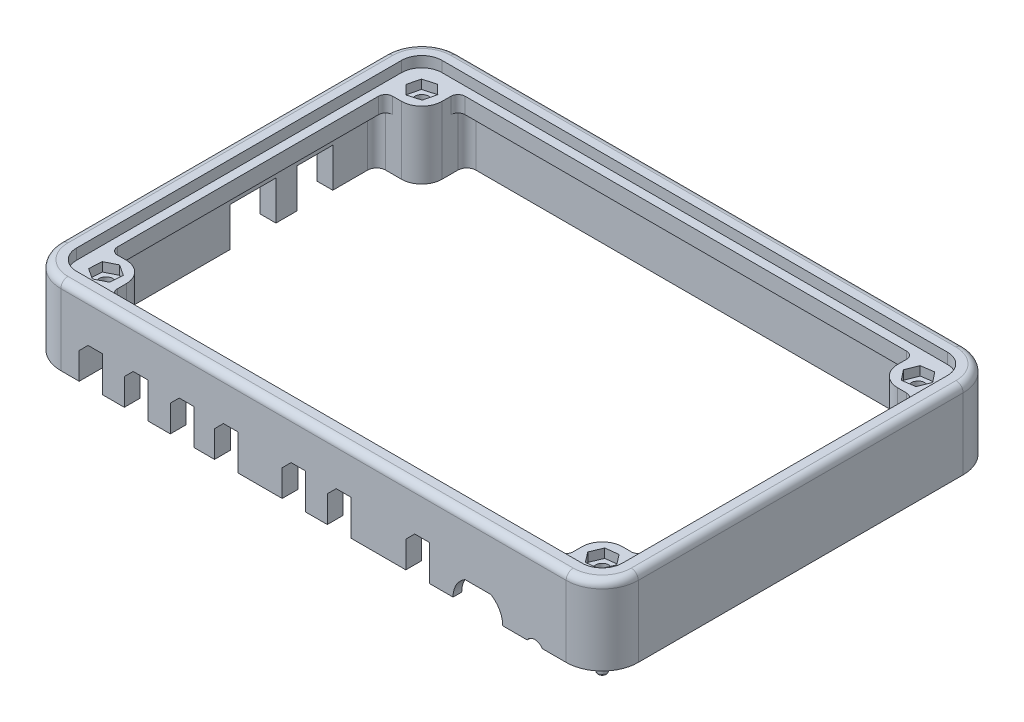
SolidWorks part; units mm, degrees
ref_plane "Front Plane" through (0, 0, 0) normal (0, 0, 1) x (1, 0, 0)
ref_plane "Top Plane" through (0, 0, 0) normal (0, 1, 0) x (1, 0, 0)
ref_plane "Right Plane" through (0, 0, 0) normal (1, 0, 0) x (0, 0, -1)
sketch "Sketch1" plane through (0, 0, 0) normal (0, 1, 0) x (1, 0, 0)
  line L1 (-71.12, 55.88) -> (71.12, 55.88)
  line L2 (-81.28, 45.72) -> (-81.28, -45.72)
  line L3 (-71.12, -55.88) -> (71.12, -55.88)
  line L4 (81.28, 45.72) -> (81.28, -45.72)
  line L5 (-81.28, 55.88) -> (81.28, -55.88) construction
  line L6 (-81.28, -55.88) -> (81.28, 55.88) construction
  arc A0 (-81.28, -45.72) -> (-71.12, -55.88) centre (-71.12, -45.72) ccw
  arc A1 (71.12, -55.88) -> (81.28, -45.72) centre (71.12, -45.72) ccw
  arc A2 (71.12, 55.88) -> (81.28, 45.72) centre (71.12, 45.72) cw
  arc A3 (-71.12, 55.88) -> (-81.28, 45.72) centre (-71.12, 45.72) ccw
  point P0 (0, 0)
  dimension "D3" = 10.16
  dimension "D1" = 162.56
  dimension "D2" = 111.76
extrude "Boss-Extrude1" add sketch "Sketch1" along normal blind 40
sketch "Sketch2" plane through (0, 0, 55.88) normal (0, 0, 1) x (1, 0, 0)
  line L0 (-71.12, 12) -> (71.12, 12) construction
  line L1 (-71.12, 40) -> (-71.12, 0) construction
  line L2 (71.12, 40) -> (71.12, 0) construction
  line L3 (71.12, 18) -> (27.6283, 18) construction
  line L4 (71.12, 28) -> (-71.12, 28) construction
  line L5 (-71.12, 40) -> (71.12, 40) construction
  line L6 (-71.12, 0) -> (71.12, 0) construction
  line L7 (-71.12, 11) -> (71.12, 11) construction
  line L8 (50.798, 16.68) -> (71.12, 16.68) construction
  line L9 (71.12, 9.42) -> (-71.12, 9.42) construction
  line L10 (76.28, 40) -> (76.28, 0) construction
  line L11 (-76.28, 40) -> (-76.28, 0) construction
  line L12 (-81.28, 40) -> (-81.28, 0) construction
  line L13 (81.28, 40) -> (81.28, 0) construction
  line L14 (42.6205, 23.9657) -> (49.9447, 23.9657)
  line L16 (-65.96, 28) -> (-59.356, 28)
  line L17 (-65.96, 28) -> (-65.96, 12)
  line L18 (-65.96, 12) -> (-59.356, 12)
  line L19 (-59.356, 28) -> (-59.356, 12)
  line L20 (-53.26, 28) -> (-46.656, 28)
  line L21 (-53.26, 28) -> (-53.26, 12)
  line L22 (-53.26, 12) -> (-46.656, 12)
  line L23 (-46.656, 28) -> (-46.656, 12)
  line L24 (-40.306, 28) -> (-33.702, 28)
  line L25 (-40.306, 28) -> (-40.306, 12)
  line L26 (-40.306, 12) -> (-33.702, 12)
  line L27 (-33.702, 28) -> (-33.702, 12)
  line L28 (-27.86, 28) -> (-21.256, 28)
  line L29 (-27.86, 28) -> (-27.86, 12)
  line L30 (-27.86, 12) -> (-21.256, 12)
  line L31 (-21.256, 28) -> (-21.256, 12)
  line L32 (-8.81, 28) -> (-2.206, 28)
  line L33 (-8.81, 28) -> (-8.81, 12)
  line L34 (-8.81, 12) -> (-2.206, 12)
  line L35 (-2.206, 28) -> (-2.206, 12)
  line L36 (3.89, 28) -> (10.494, 28)
  line L37 (3.89, 28) -> (3.89, 12)
  line L38 (3.89, 12) -> (10.494, 12)
  line L39 (10.494, 28) -> (10.494, 12)
  line L40 (25.988, 28) -> (32.592, 28)
  line L41 (25.988, 28) -> (25.988, 12)
  line L42 (25.988, 12) -> (32.592, 12)
  line L43 (32.592, 28) -> (32.592, 12)
  circle A0 centre (62.28, 16.68) radius 2.5
  circle A1 centre (46.2826, 18) radius 7 construction
  arc A2 (42.6205, 23.9657) -> (49.9447, 23.9657) centre (46.2826, 18) ccw
  dimension "D9" = 5
  dimension "D11" = 14
  dimension "D1" = 12
  dimension "D2" = 12
  dimension "D3" = 1
  dimension "D4" = 1.58
  dimension "D5" = 7
  dimension "D6" = 5.68
  dimension "D7" = 5
  dimension "D8" = 5
  dimension "D10" = 14
  dimension "D12" = 29.9974
  dimension "D13" = 6.604
  dimension "D14" = 135.636
  dimension "D15" = 6.604
  dimension "D16" = 122.936
  dimension "D17" = 6.604
  dimension "D18" = 109.982
  dimension "D19" = 6.604
  dimension "D20" = 97.536
  dimension "D21" = 6.604
  dimension "D22" = 78.486
  dimension "D23" = 6.604
  dimension "D24" = 65.786
  dimension "D25" = 6.604
  dimension "D26" = 43.688
sketch "Sketch3" plane through (-81.28, 0, 0) normal (-1, 0, 0) x (0, 0, 1)
  line L0 (-55.88, 11) -> (55.88, 11) construction
  line L1 (-55.88, 40) -> (-55.88, 0) construction
  line L2 (55.88, 40) -> (55.88, 0) construction
  line L3 (-45.72, 0) -> (45.72, 0) construction
  line L4 (55.88, 40) -> (55.88, 0) construction
  line L5 (55.88, 9.42) -> (-55.88, 9.42) construction
  line L6 (-50.88, 40) -> (-50.88, 0) construction
  line L7 (-45.72, 40) -> (-55.88, 40) construction
  line L8 (-55.88, 0) -> (-45.72, 0) construction
  line L9 (50.88, 40) -> (50.88, 0) construction
  line L10 (55.88, 40) -> (45.72, 40) construction
  line L11 (45.72, 0) -> (55.88, 0) construction
  line L13 (-26.38, 17) -> (-16.38, 17)
  line L14 (-26.38, 17) -> (-26.38, 29)
  line L15 (-26.38, 29) -> (-16.38, 29)
  line L16 (-16.38, 17) -> (-16.38, 29)
  line L17 (-10.38, 29) -> (2.62, 29)
  line L18 (-10.38, 29) -> (-10.38, 17)
  line L19 (-10.38, 17) -> (2.62, 17)
  line L20 (2.62, 29) -> (2.62, 17)
  dimension "D1" = 5
  dimension "D2" = 5
  dimension "D3" = 9.42
  dimension "D4" = 1.58
  dimension "D5" = 24.5
  dimension "D6" = 6
  dimension "D7" = 12
  dimension "D8" = 10
  dimension "D9" = 6
  dimension "D10" = 13
  dimension "D11" = 12
extrude "Cut-Extrude1" cut sketch "Sketch2" against normal blind 40
extrude "Cut-Extrude2" cut sketch "Sketch3" against normal blind 40
sketch "Sketch4" plane through (0, 0, 55.88) normal (0, 0, 1) x (1, 0, 0)
  line L6 (88.1928, 18) -> (-91.2841, 18)
  line L7 (88.1928, 18) -> (88.1928, -8.3971)
  line L8 (88.1928, -8.3971) -> (-91.2841, -8.3971)
  line L9 (-91.2841, 18) -> (-91.2841, -8.3971)
extrude "Cut-Extrude3" cut sketch "Sketch4" against normal blind 120
fillet "Fillet1" radius 2 8 edges at (-81.28, 40, 0) (-78.3042, 40, -52.9042) (0, 40, -55.88) (78.3042, 40, -52.9042) (81.28, 40, 0) (78.3042, 40, 52.9042) (0, 40, 55.88) (-78.3042, 40, 52.9042)
sketch "Sketch5" plane through (0, 40, 0) normal (0, -1, 0) x (1, 0, 0)
  line L1 (-71.12, 51.435) -> (71.12, 51.435)
  line L2 (-76.835, 45.72) -> (-76.835, -45.72)
  line L3 (-71.12, -51.435) -> (71.12, -51.435)
  line L4 (76.835, 45.72) -> (76.835, -45.72)
  line L5 (-76.835, 51.435) -> (76.835, -51.435) construction
  line L6 (-76.835, -51.435) -> (76.835, 51.435) construction
  arc A0 (-76.835, -45.72) -> (-71.12, -51.435) centre (-71.12, -45.72) ccw
  arc A1 (71.12, -51.435) -> (76.835, -45.72) centre (71.12, -45.72) ccw
  arc A2 (71.12, 51.435) -> (76.835, 45.72) centre (71.12, 45.72) cw
  arc A3 (-71.12, 51.435) -> (-76.835, 45.72) centre (-71.12, 45.72) ccw
  point P0 (0, 0)
  dimension "D3" = 5.715
  dimension "D1" = 102.87
  dimension "D2" = 153.67
extrude "Cut-Extrude5" cut sketch "Sketch5" along normal blind 2.9972
sketch "Sketch6" plane through (0, 37.0028, 0) normal (0, 1, 0) x (1, 0, 0)
  line L0 (71.12, -51.435) -> (-71.12, -51.435) construction
  line L1 (-61.595, 51.435) -> (61.595, 51.435)
  line L2 (-64.135, 51.435) -> (-64.135, -51.435) construction
  line L3 (-61.595, -51.435) -> (61.595, -51.435)
  line L4 (64.135, 51.435) -> (64.135, -51.435) construction
  line L5 (-64.135, 51.435) -> (64.135, -51.435) construction
  line L6 (-64.135, -51.435) -> (64.135, 51.435) construction
  line L7 (76.835, 45.72) -> (76.835, -45.72) construction
  line L8 (-76.835, 38.735) -> (76.835, 38.735) construction
  line L9 (-76.835, 36.195) -> (-76.835, -36.195)
  line L10 (-76.835, -38.735) -> (76.835, -38.735) construction
  line L11 (76.835, 36.195) -> (76.835, -36.195)
  line L12 (-76.835, 38.735) -> (76.835, -38.735) construction
  line L13 (-76.835, -38.735) -> (76.835, 38.735) construction
  line L14 (-76.835, -45.72) -> (-76.835, 45.72) construction
  line L15 (-71.12, 51.435) -> (71.12, 51.435) construction
  line L16 (-71.12, 51.435) -> (71.12, 51.435) construction
  line L17 (-74.295, 38.735) -> (-69.85, 38.735)
  line L18 (-64.135, 44.45) -> (-64.135, 48.895)
  line L19 (64.135, 48.895) -> (64.135, 44.45)
  line L20 (69.85, 38.735) -> (74.295, 38.735)
  line L21 (74.295, -38.735) -> (69.85, -38.735)
  line L22 (64.135, -44.45) -> (64.135, -48.895)
  line L23 (-74.295, -38.735) -> (-69.85, -38.735)
  line L24 (-64.135, -44.45) -> (-64.135, -48.895)
  line L25 (71.12, -51.435) -> (-71.12, -51.435) construction
  line L26 (76.835, 45.72) -> (76.835, -45.72) construction
  arc A0 (69.85, -38.735) -> (64.135, -44.45) centre (69.85, -44.45) ccw
  arc A1 (64.135, 44.45) -> (69.85, 38.735) centre (69.85, 44.45) ccw
  arc A2 (-69.85, 38.735) -> (-64.135, 44.45) centre (-69.85, 44.45) ccw
  arc A3 (-69.85, -38.735) -> (-64.135, -44.45) centre (-69.85, -44.45) cw
  arc A4 (61.595, -51.435) -> (64.135, -48.895) centre (61.595, -48.895) ccw
  arc A5 (74.295, -38.735) -> (76.835, -36.195) centre (74.295, -36.195) ccw
  arc A6 (74.295, 38.735) -> (76.835, 36.195) centre (74.295, 36.195) cw
  arc A7 (61.595, 51.435) -> (64.135, 48.895) centre (61.595, 48.895) cw
  arc A8 (-61.595, 51.435) -> (-64.135, 48.895) centre (-61.595, 48.895) ccw
  arc A9 (-74.295, 38.735) -> (-76.835, 36.195) centre (-74.295, 36.195) ccw
  arc A10 (-64.135, -48.895) -> (-61.595, -51.435) centre (-61.595, -48.895) ccw
  arc A11 (-76.835, -36.195) -> (-74.295, -38.735) centre (-74.295, -36.195) ccw
  circle A12 centre (-69.85, 44.45) radius 1.905
  circle A13 centre (69.85, 44.45) radius 1.905
  circle A14 centre (69.85, -44.45) radius 1.905
  circle A15 centre (-69.85, -44.45) radius 1.905
  point P0 (0, 0)
  point P8 (0, 0)
  point P25 (64.135, -38.735)
  point P28 (64.135, 38.735)
  point P31 (-64.135, 38.735)
  point P34 (-64.135, -38.735)
  dimension "D3" = 5.715
  dimension "D4" = 2.54
  dimension "D7" = 3.81
  dimension "D10" = 3.81
  dimension "D13" = 3.81
  dimension "D16" = 3.81
  dimension "D1" = 12.7
  dimension "D2" = 12.7
  dimension "D5" = 6.985
  dimension "D6" = 6.985
  dimension "D8" = 6.985
  dimension "D9" = 6.985
  dimension "D11" = 6.985
  dimension "D12" = 6.985
  dimension "D14" = 6.985
  dimension "D15" = 6.985
extrude "Cut-Extrude6" cut sketch "Sketch6" against normal blind 25.8572
sketch "Sketch8" plane through (0, 18, 0) normal (0, -1, 0) x (1, 0, 0)
  line L0 (-81.28, 2.62) -> (-81.28, 45.72) construction
  line L1 (-65.96, 55.88) -> (-71.12, 55.88) construction
  circle A0 centre (-76.2, 50.8) radius 1.27
  dimension "D3" = 2.54
  dimension "D1" = 5.08
  dimension "D2" = 5.08
extrude "Boss-Extrude2" add sketch "Sketch8" along normal blind 2.5
mirror "Mirror1" about plane through (0, 0, 0) normal (0, 0, 1) of "Boss-Extrude2"
mirror "Mirror2" about plane through (0, 0, 0) normal (1, 0, 0) of "Mirror1", "Boss-Extrude2"
fillet "Fillet2" radius 0.508 8 edges at (76.2, 18, 49.53) (76.2, 15.5, 49.53) (76.2, 15.5, -49.53) (76.2, 18, -49.53) (-76.2, 15.5, -49.53) (-76.2, 18, -49.53) (-76.2, 15.5, 49.53) (-76.2, 18, 52.07)
chamfer "Chamfer1" distance 2.5 angle 45 7 edges at (-65.96, 28, 48.0716) (-53.26, 28, 53.6575) (-40.306, 28, 53.6575) (-27.86, 28, 53.6575) (-8.81, 28, 53.6575) (3.89, 28, 53.6575) (25.988, 28, 53.6575)
sketch "Sketch9" plane through (0, 37.0028, 0) normal (0, 1, 0) x (1, 0, 0)
  line L0 (-71.12, 51.435) -> (-61.595, 51.435) construction
  line L1 (-66.3575, 51.435) -> (67.5812, 51.435)
  line L2 (-66.3575, 51.435) -> (-66.3575, 48.935)
  line L3 (-66.3575, 48.935) -> (67.5812, 48.935)
  line L4 (67.5812, 51.435) -> (67.5812, 48.935)
  line L5 (76.835, 45.72) -> (76.835, -45.72) construction
  line L6 (74.335, 40.9859) -> (76.835, 40.9859)
  line L7 (74.335, 40.9859) -> (74.335, -43.9005)
  line L8 (74.335, -43.9005) -> (76.835, -43.9005)
  line L9 (76.835, 40.9859) -> (76.835, -43.9005)
  line L10 (-61.595, -51.435) -> (-71.12, -51.435) construction
  line L11 (67.5812, -48.935) -> (-67.5812, -48.935)
  line L12 (67.5812, -48.935) -> (67.5812, -51.435)
  line L13 (67.5812, -51.435) -> (-67.5812, -51.435)
  line L14 (-67.5812, -48.935) -> (-67.5812, -51.435)
  line L15 (-76.835, -45.72) -> (-76.835, 45.72) construction
  line L16 (-74.335, -41.7146) -> (-76.835, -41.7146)
  line L17 (-74.335, -41.7146) -> (-74.335, 42.6254)
  line L18 (-74.335, 42.6254) -> (-76.835, 42.6254)
  line L19 (-76.835, -41.7146) -> (-76.835, 42.6254)
  dimension "D1" = 2.5
  dimension "D2" = 2.5
  dimension "D3" = 2.5
  dimension "D4" = 2.5
extrude "Boss-Extrude3" add sketch "Sketch9" against normal blind 4.5
fillet "Fillet3" radius 2 8 edges at (-64.1347, 34.7528, 48.935) (-74.335, 34.7528, 38.7347) (64.1347, 34.7528, 48.935) (74.335, 34.7528, 38.7347) (74.335, 34.7528, -38.7347) (64.1347, 34.7528, -48.935) (-64.1347, 34.7528, -48.935) (-74.335, 34.7528, -38.7347)
sketch "Sketch10" plane through (0, 18, 0) normal (0, -1, 0) x (1, 0, 0)
  line L0 (76.835, 36.195) -> (76.835, -36.195) construction
  line L1 (-68.135, 53.735) -> (68.135, 53.735)
  line L2 (-79.135, 42.735) -> (-79.135, -42.735)
  line L3 (-68.135, -53.735) -> (68.135, -53.735)
  line L4 (79.135, 42.735) -> (79.135, -42.735)
  line L5 (-79.135, 53.735) -> (79.135, -53.735) construction
  line L6 (-79.135, -53.735) -> (79.135, 53.735) construction
  line L7 (-61.595, 51.435) -> (61.595, 51.435) construction
  line L8 (-79.135, 42.735) -> (-68.135, 53.735)
  line L9 (68.135, 53.735) -> (79.135, 42.735)
  line L10 (68.135, -53.735) -> (79.135, -42.735)
  line L11 (-79.135, -42.735) -> (-68.135, -53.735)
  line L12 (-77.0024, -41.6024) -> (-67.0024, -51.6024)
  line L13 (-67.0024, 51.6024) -> (67.0024, 51.6024)
  line L14 (-77.0024, 41.6024) -> (-77.0024, -41.6024)
  line L15 (-67.0024, -51.6024) -> (67.0024, -51.6024)
  line L16 (77.0024, 41.6024) -> (77.0024, -41.6024)
  line L17 (-77.0024, 51.6024) -> (77.0024, -51.6024) construction
  line L18 (-77.0024, -51.6024) -> (77.0024, 51.6024) construction
  line L19 (67.0024, -51.6024) -> (77.0024, -41.6024)
  line L20 (67.0024, 51.6024) -> (77.0024, 41.6024)
  line L21 (-77.0024, 41.6024) -> (-67.0024, 51.6024)
  point P0 (0, 0)
  point P18 (0, 0)
  dimension "D1" = 2.3
  dimension "D2" = 2.3
  dimension "D9" = 11
  dimension "D10" = 11
  dimension "D11" = 11
  dimension "D12" = 11
  dimension "D13" = 10
  dimension "D14" = 10
  dimension "D15" = 10
  dimension "D16" = 10
extrude "Boss-Extrude4" [suppressed] add sketch "Sketch10" along normal blind 2.5
sketch "Sketch13" plane through (0, 0, 51.435) normal (0, 0, -1) x (-1, 0, 0)
  line L1 (-56.7826, 28.5) -> (-35.7826, 28.5)
  line L2 (-56.7826, 28.5) -> (-56.7826, 7.5)
  line L3 (-56.7826, 7.5) -> (-35.7826, 7.5)
  line L4 (-35.7826, 28.5) -> (-35.7826, 7.5)
  line L5 (-56.7826, 28.5) -> (-35.7826, 7.5) construction
  line L6 (-56.7826, 7.5) -> (-35.7826, 28.5) construction
  point P0 (-46.2826, 18)
  dimension "D1" = 21
  dimension "D2" = 21
extrude "Cut-Extrude7" cut sketch "Sketch13" against normal blind 2
sketch "Sketch14" plane through (0, 37.0028, 0) normal (0, 1, 0) x (1, 0, 0)
  line L1 (-67.2268, 41.9304) -> (-66.3563, 45.462)
  line L2 (-66.3563, 45.462) -> (-68.9795, 47.9816)
  line L3 (-68.9795, 47.9816) -> (-72.4732, 46.9696)
  line L4 (-72.4732, 46.9696) -> (-73.3437, 43.438)
  line L5 (-73.3437, 43.438) -> (-70.7205, 40.9184)
  line L6 (-70.7205, 40.9184) -> (-67.2268, 41.9304)
  line L7 (72.1064, 41.5971) -> (73.4488, 44.9776)
  line L8 (73.4488, 44.9776) -> (71.1925, 47.8305)
  line L9 (71.1925, 47.8305) -> (67.5936, 47.3029)
  line L10 (67.5936, 47.3029) -> (66.2512, 43.9224)
  line L11 (66.2512, 43.9224) -> (68.5075, 41.0695)
  line L12 (68.5075, 41.0695) -> (72.1064, 41.5971)
  line L13 (72.0495, -47.3469) -> (73.4586, -43.9936)
  line L14 (73.4586, -43.9936) -> (71.2591, -41.0967)
  line L15 (71.2591, -41.0967) -> (67.6505, -41.5531)
  line L16 (67.6505, -41.5531) -> (66.2414, -44.9064)
  line L17 (66.2414, -44.9064) -> (68.4409, -47.8033)
  line L18 (68.4409, -47.8033) -> (72.0495, -47.3469)
  line L19 (-66.8113, -46.4491) -> (-66.5994, -42.818)
  line L20 (-66.5994, -42.818) -> (-69.638, -40.8189)
  line L21 (-69.638, -40.8189) -> (-72.8887, -42.4509)
  line L22 (-72.8887, -42.4509) -> (-73.1006, -46.082)
  line L23 (-73.1006, -46.082) -> (-70.062, -48.0811)
  line L24 (-70.062, -48.0811) -> (-66.8113, -46.4491)
  circle A0 centre (-69.85, 44.45) radius 3.15 construction
  circle A1 centre (69.85, 44.45) radius 3.15 construction
  circle A2 centre (69.85, -44.45) radius 3.15 construction
  circle A3 centre (-69.85, -44.45) radius 3.15 construction
  dimension "D1" = 6.3
  dimension "D2" = 6.3
  dimension "D3" = 6.3
  dimension "D4" = 6.3
extrude "Cut-Extrude8" cut sketch "Sketch14" against normal blind 2.54
